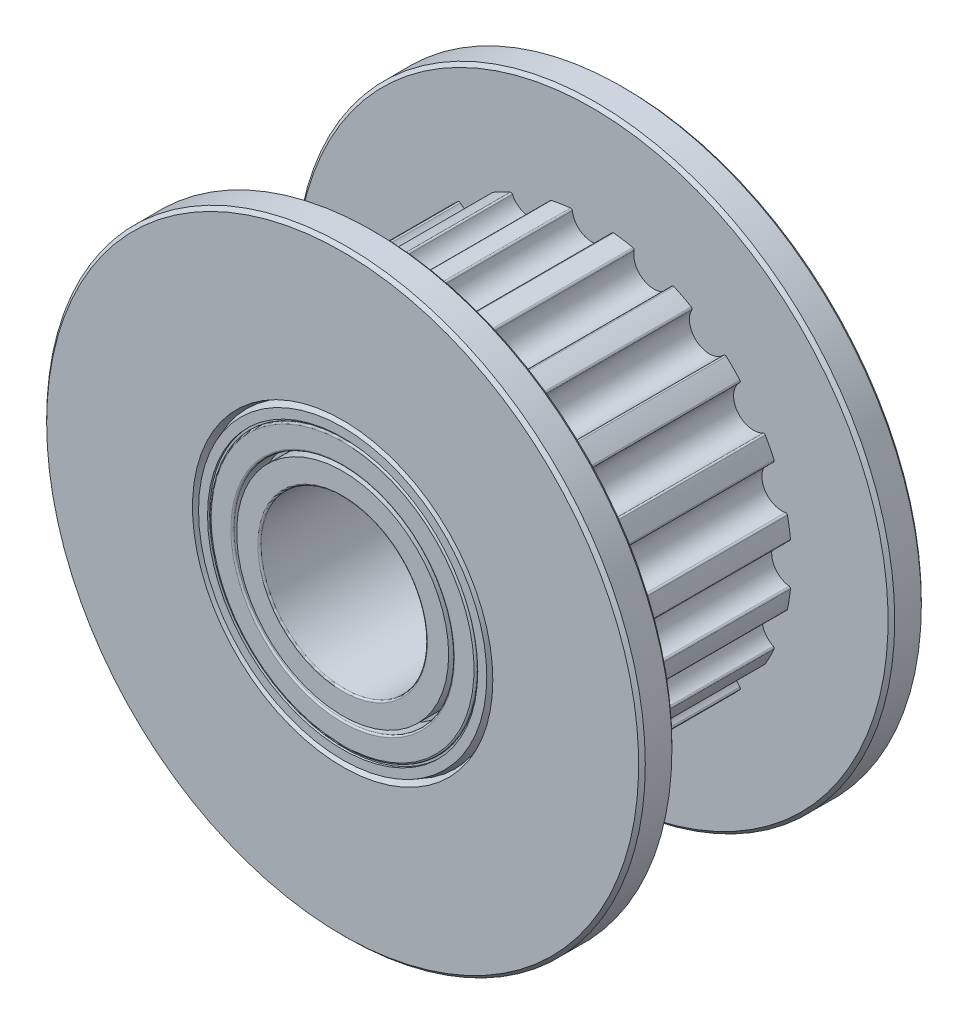
SolidWorks part; units mm, degrees
ref_plane "Front" through (0, 0, 0) normal (0, 0, 1) x (1, 0, 0)
ref_plane "Top" through (0, 0, 0) normal (0, 1, 0) x (1, 0, 0)
ref_plane "Right" through (0, 0, 0) normal (1, 0, 0) x (0, 0, -1)
sketch "Sketch1" plane through (0, 0, 0) normal (1, 0, 0) x (0, 0, -1)
  line L0 (-4.25, 0) -> (4.25, 0) construction
  line L1 (4.25, 9) -> (4.25, -9) construction
  line L2 (4.25, 9) -> (3.25, 9) construction
  line L3 (4.25, 2.5) -> (4.25, -2.5) construction
  line L4 (4.25, 6) -> (4.25, -6) construction
  line L5 (3.25, 0) -> (-3.25, 0) construction
  line L6 (3.25, 9) -> (3.25, 6) construction
  point P12 (3.25, 7)
  point P14 (3.25, 7)
  dimension "Width" = 8.5
  dimension "OD" = 18
  dimension "D3" = 1
  dimension "ID" = 5
  dimension "Diameter" = 12
  dimension "Max Belt Width" = 6.5
  dimension "Groove Depth" = 3
sketch "Sketch2" plane through (0, 0, 0) normal (1, 0, 0) x (0, 0, -1)
  line L0 (4.25, 2.5) -> (0, 2.5)
  line L1 (4.25, 2.5) -> (4.25, 3.1875)
  line L2 (4.25, 9) -> (4.25, -9) construction
  line L3 (4.25, 3.1875) -> (3.5625, 3.1875) construction
  line L4 (3.9062, 3.3125) -> (3.9062, 3.1875) construction
  line L5 (4.25, 4) -> (0, 4)
  line L6 (3.5625, 3.3125) -> (3.5625, 3.1875)
  line L7 (4.25, 4) -> (4.25, 3.3125)
  line L8 (4.25, 3.3125) -> (3.5625, 3.3125)
  line L9 (3.5625, 3.3125) -> (3.5625, 3.1875) construction
  line L10 (0, 4) -> (0, 2.5)
  line L11 (3.9062, 3.1875) -> (4.25, 3.1875)
  line L12 (3.5625, 3.1875) -> (3.9062, 3.1875)
  dimension "D1" = 2
  dimension "D2" = 0.125
revolve "Revolve1" add sketch "Sketch2" angle 360 about L0
mirror "Mirror1" about plane through (0, 0, 0) normal (0, 0, 1) of bodies 108
sketch "Sketch3" plane through (0, 0, 0) normal (1, 0, 0) x (0, 0, -1)
  line L0 (3.25, 9) -> (4.25, 9)
  line L1 (4.25, 9) -> (4.25, 4.5153)
  line L2 (4.25, 9) -> (4.25, -9) construction
  line L3 (4.25, 4.5153) -> (4, 4.4243)
  line L4 (4, 4.4243) -> (4.25, 4.3333)
  line L5 (4.25, 4.3333) -> (4.25, 4.0625)
  line L6 (4.1875, 4) -> (4.1875, 4.0625)
  line L7 (4.25, 4) -> (-4.25, 4) construction
  line L8 (4.1875, 4.0625) -> (4.25, 4.0625)
  line L9 (3.25, 9) -> (3.25, 6)
  line L10 (3.25, 6) -> (-3.25, 6)
  line L11 (0, 6) -> (0, 4) construction
  line L12 (-4.1875, 4) -> (4.1875, 4)
  line L13 (-3.25, 9) -> (-3.25, 6)
  line L14 (-4.1875, 4.0625) -> (-4.25, 4.0625)
  line L15 (-4.1875, 4) -> (-4.1875, 4.0625)
  line L16 (-4.25, 4.3333) -> (-4.25, 4.0625)
  line L17 (-4, 4.4243) -> (-4.25, 4.3333)
  line L18 (-4.25, 4.5153) -> (-4, 4.4243)
  line L19 (-4.25, 9) -> (-4.25, 4.5153)
  line L20 (-3.25, 9) -> (-4.25, 9)
  line L21 (4, 4.4243) -> (4.25, 4.4243) construction
  line L22 (4.125, 4.4243) -> (4.125, 4) construction
  dimension "D1" = 40
  dimension "D2" = 0.25
  dimension "D3" = 0.0625
  dimension "D4" = 0.3333
revolve "Revolve2" add sketch "Sketch3" angle 360 about L0
sketch "Sketch4" plane through (0, 0, 0) normal (0, 0, 1) x (1, 0, 0)
  line L0 (-0.6, 6) -> (0.6, 6)
  line L1 (-0.6, 6) -> (-0.6, 4.8) construction
  line L2 (-0.6, 4.8) -> (0.6, 4.8) construction
  line L3 (0.6, 4.8) -> (0.6, 6) construction
  line L4 (0, 6) -> (0, 4.8) construction
  arc A0 (0.6, 6) -> (-0.6, 6) centre (0, 6) cw
  dimension "D1" = 1.2
  dimension "D3" = 1.2
extrude "Cut-Extrude1" cut sketch "Sketch4" against normal up to surface and the other way up to surface up to face at (6, 0, -3.25) other way up to face at (9, 0, 3.25)
fillet "Fillet1" radius 0.05 2 edges at (0.5992, 5.97, 0) (-0.5992, 5.97, 0)
pattern_circular "CirPattern3" count 20 over 360 about axis through (0, 0, -3.25) along (0, 0, 1) of "Cut-Extrude1", "Fillet1"
chamfer "Chamfer1" distance 0.1 angle 45 4 edges at (9, 0, -4.25) (9, 0, -3.25) (9, 0, 3.25) (9, 0, 4.25)
fillet "Fillet2" radius 0.05 7 edges at (4, 0, 4.25) (3.3125, 0, 4.25) (2.5, 0, 4.25) (2.5, 0, -4.25) (4, 0, -4.25) (3.3125, 0, -4.25) (3.1875, 0, -4.25)
combine bodies "Combine1" operation type add bodies to combine 113 109
ref_axis "Center Axis 1" through (0, 0, -4.2) along (0, 0, 1)
ref_plane "Contact Plane 1" through (0, 0, -3.25) normal (0, 0, 1) x (1, 0, 0)
ref_plane "Contact Plane 2" through (0, 0, 3.25) normal (0, 0, 1) x (1, 0, 0)
equation "\"D1@Sketch4\"=\"Groove Depth@Sketch1\"/2.5"
equation "\"D3@Sketch4\"=\"Diameter@Sketch1\"/10"
equation "\"D2@Sketch3\"=\"D3@Sketch1\"/4"
equation "\"D3@Sketch3\"=\"D2@Sketch3\"/4"
equation "\"D4@Sketch3\"=\"D3@Sketch1\"/3"
equation "\"D1\"=0.5"
equation "\"D2@Sketch2\"=\"D1\"/4"
